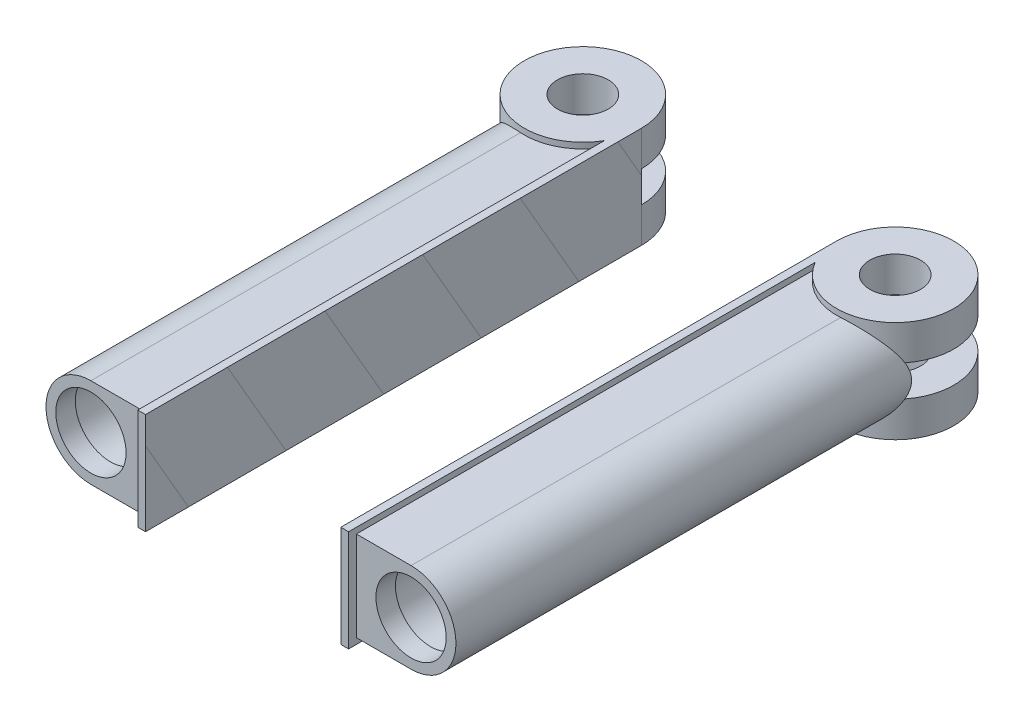
SolidWorks part; units mm, degrees
ref_plane "Front Plane" through (0, 0, 0) normal (0, 0, 1) x (1, 0, 0)
ref_plane "Top Plane" through (0, 0, 0) normal (0, 1, 0) x (1, 0, 0)
ref_plane "Right Plane" through (0, 0, 0) normal (1, 0, 0) x (0, 0, -1)
sketch "Sketch1" plane through (0, 0, 0) normal (0, 1, 0) x (1, 0, 0)
  circle A0 centre (0, 0) radius 30
  dimension "D1" = 60
extrude "Boss-Extrude1" add sketch "Sketch1" along normal mid plane 52
sketch "Sketch3" plane through (0, 0, 0) normal (0, 0, 1) x (1, 0, 0)
  line L1 (26, 23) -> (-2, 23)
  line L2 (30, 26) -> (30, -26)
  line L3 (26, -23) -> (-2, -23)
  line L4 (30, -26) -> (26, -26)
  line L7 (-30, -26) -> (30, -26) construction
  line L8 (26, -26) -> (26, -23)
  line L9 (30, 26) -> (26, 26)
  line L10 (30, 26) -> (-30, 26) construction
  line L11 (26, 26) -> (26, 23)
  arc A0 (-2, 23) -> (-2, -23) centre (-2, 0) ccw
  dimension "D4" = 28
  dimension "D1" = 4
  dimension "D2" = 3
  dimension "D3" = 3
  dimension "D5" = 4
extrude "Boss-Extrude2" add sketch "Sketch3" along normal blind 250 contours A0 | L1 L3 region at (4.945, 0, 0)
sketch "Sketch4" plane through (0, 0, 0) normal (0, 1, 0) x (1, 0, 0)
  circle A0 centre (0, 0) radius 13
  dimension "D1" = 26
extrude "Cut-Extrude2" cut sketch "Sketch4" against normal mid plane 52
extrude "Cut-Extrude3" cut sketch "Sketch1<2>" against normal blind 8
sketch "Sketch1<2>" plane through (0, 0, 0) normal (0, 1, 0) x (1, 0, 0) same geometry as "Sketch1"
extrude "Cut-Extrude4" cut sketch "Sketch1<3>" along normal blind 8
sketch "Sketch1<3>" plane through (0, 0, 0) normal (0, 1, 0) x (1, 0, 0) same geometry as "Sketch1"
sketch "Sketch5" plane through (0, 0, 250) normal (0, 0, 1) x (1, 0, 0)
  circle A0 centre (-2, 0) radius 19
  arc A2 (-2, 23) -> (-2, -23) centre (-2, 0) ccw construction
  dimension "D1" = 38
extrude "Cut-Extrude5" cut sketch "Sketch5" against normal blind 210
sketch "Sketch7" plane through (0, 0, 0) normal (0, 1, 0) x (1, 0, 0)
  line L0 (26, -250) -> (26, -254)
  line L1 (26, -254) -> (30, -254)
  line L2 (30, -254) -> (30, -250)
  line L3 (26, -250) -> (30, -250)
  dimension "D1" = 4
extrude "Boss-Extrude4" add sketch "Sketch7" along normal mid plane 52
sketch "Sketch8" plane through (30, 0, 0) normal (1, 0, 0) x (0, 0, -1)
  line L0 (-12.0631, 26) -> (0, 5.1061)
  line L2 (-62.0631, 26) -> (-32.0409, -26)
  line L3 (-112.0631, 26) -> (-82.0409, -26)
  line L4 (-162.0631, 26) -> (-132.0409, -26)
  line L5 (-212.0631, 26) -> (-182.0409, -26)
  line L6 (-254, 12.0343) -> (-232.0409, -26)
  line L8 (-254, 26) -> (0, 26)
  line L9 (-254, 26) -> (-254, -26)
  line L10 (-254, -26) -> (0, -26)
  line L11 (0, 26) -> (0, -26)
  dimension "D2" = 6
split line "Split Line1"
sketch "Sketch9" plane through (0, 0, 250) normal (0, 0, 1) x (1, 0, 0)
  circle A0 centre (-2, 0) radius 19
  circle A1 centre (-2, 0) radius 19 construction
  circle A2 centre (-2, 0) radius 18
  dimension "D1" = 36
extrude "Boss-Extrude5" add sketch "Sketch9" against normal blind 10
ref_plane "Plane1" through (80, 0, 0) normal (1, 0, 0) x (0, 0, -1)
mirror "Mirror2" about plane through (80, 0, 0) normal (1, 0, 0) of bodies 112
